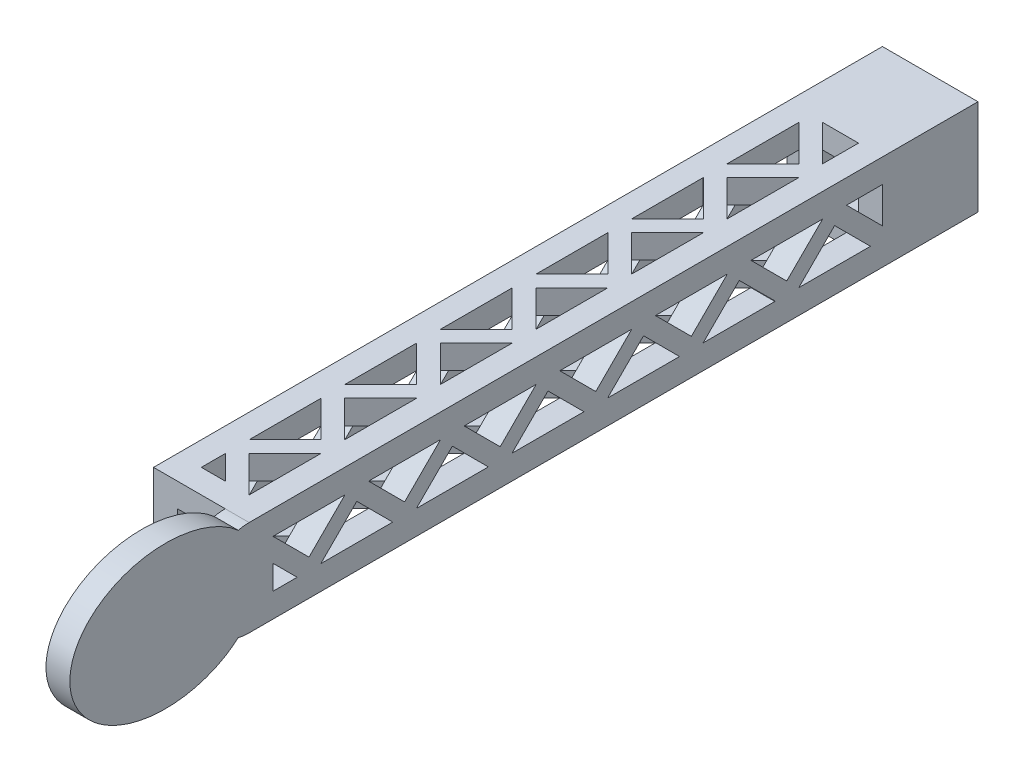
SolidWorks part; units mm, degrees
ref_plane "Front Plane" through (0, 0, 0) normal (0, 0, 1) x (1, 0, 0)
ref_plane "Top Plane" through (0, 0, 0) normal (0, 1, 0) x (1, 0, 0)
ref_plane "Right Plane" through (0, 0, 0) normal (1, 0, 0) x (0, 0, -1)
sketch "Sketch1" plane through (0, 0, 0) normal (0, 0, 1) x (1, 0, 0)
  line L1 (0, 0) -> (20.32, 0)
  line L2 (0, 0) -> (0, 20.32)
  line L3 (0, 20.32) -> (20.32, 20.32)
  line L4 (20.32, 0) -> (20.32, 20.32)
  line L5 (5.08, 15.24) -> (15.24, 15.24)
  line L6 (5.08, 15.24) -> (5.08, 5.08)
  line L7 (5.08, 5.08) -> (15.24, 5.08)
  line L8 (15.24, 15.24) -> (15.24, 5.08)
  dimension "D1" = 20.32
  dimension "D2" = 20.32
  dimension "D3" = 10.16
  dimension "D4" = 10.16
  dimension "D5" = 5.08
  dimension "D6" = 5.08
extrude "Boss-Extrude1" add sketch "Sketch1" along normal blind 154.94
sketch "Sketch6" plane through (0, 20.32, 0) normal (0, 1, 0) x (1, 0, 0)
  line L0 (20.32, 0) -> (20.32, -20.32) construction
  line L1 (20.32, -154.94) -> (20.32, 0) construction
  line L2 (20.32, -20.32) -> (15.24, -20.32) construction
  line L3 (0, 0) -> (0, -20.32) construction
  line L4 (0, -154.94) -> (0, 0) construction
  line L5 (0, -20.32) -> (5.08, -20.32) construction
  line L6 (7.62, -20.32) -> (15.24, -27.94)
  line L7 (7.62, -20.32) -> (15.24, -20.32)
  line L8 (5.08, -22.86) -> (5.08, -38.1)
  line L9 (5.08, -149.86) -> (10.2137, -149.86)
  line L10 (15.24, -20.32) -> (15.24, -27.94)
  line L11 (5.08, -22.86) -> (12.7, -30.48)
  line L12 (15.24, -33.02) -> (15.24, -48.26)
  line L13 (12.7, -30.48) -> (5.08, -38.1)
  line L14 (15.24, -33.02) -> (7.62, -40.64)
  line L15 (7.62, -40.64) -> (15.24, -48.26)
  line L16 (5.1337, -43.1263) -> (12.7335, -50.7665)
  line L17 (5.08, -43.18) -> (5.08, -58.42)
  line L18 (5.1337, -43.1263) -> (5.08, -43.18)
  line L19 (15.24, -53.2863) -> (7.5931, -60.9331)
  line L20 (12.7335, -50.7665) -> (5.08, -58.42)
  line L21 (7.5931, -60.9331) -> (15.24, -68.58)
  line L22 (5.08, -63.4463) -> (12.7269, -71.0931)
  line L23 (12.7269, -71.0931) -> (5.08, -78.74)
  line L24 (15.24, -73.6063) -> (7.5931, -81.2531)
  line L25 (5.08, -83.7663) -> (12.7269, -91.4131)
  line L26 (7.5931, -81.2531) -> (15.24, -88.9)
  line L27 (15.24, -53.2863) -> (15.24, -68.58)
  line L28 (5.08, -63.4463) -> (5.08, -78.74)
  line L29 (15.24, -73.6063) -> (15.24, -88.9)
  line L30 (5.08, -83.7663) -> (5.08, -99.06)
  line L31 (15.24, -93.9263) -> (15.24, -109.22)
  line L32 (15.24, -93.9263) -> (7.5931, -101.5731)
  line L33 (12.7269, -91.4131) -> (5.08, -99.06)
  line L34 (7.5931, -101.5731) -> (15.24, -109.22)
  line L35 (5.08, -104.0863) -> (12.7269, -111.7331)
  line L36 (12.7269, -111.7331) -> (5.08, -119.38)
  line L37 (15.24, -114.2463) -> (7.5931, -121.8931)
  line L38 (7.5931, -121.8931) -> (15.24, -129.54)
  line L39 (5.08, -124.4063) -> (12.7269, -132.0531)
  line L40 (12.7269, -132.0531) -> (5.08, -139.7)
  line L41 (15.24, -134.5663) -> (7.5931, -142.2131)
  line L42 (5.08, -144.7263) -> (10.2137, -149.86)
  line L43 (7.5931, -142.2131) -> (15.24, -149.86)
  line L44 (5.08, -144.7263) -> (5.08, -149.86)
  line L45 (15.24, -134.5663) -> (15.24, -149.86)
  line L46 (5.08, -124.4063) -> (5.08, -139.7)
  line L47 (15.24, -114.2463) -> (15.24, -129.54)
  line L48 (5.08, -104.0863) -> (5.08, -119.38)
  line M9 (20.32, 0) -> (0, 0)
  line M10 (0, 0) -> (0, -154.94)
  line M11 (0, -154.94) -> (20.32, -154.94)
  line M12 (20.32, -154.94) -> (20.32, 0)
  dimension "D1" = 20.32
  dimension "D2" = 5.08
  dimension "D3" = 5.08
  dimension "D4" = 20.32
  dimension "D5" = 129.54
  dimension "D7" = 10.16
  dimension "D8" = 7.62
  dimension "D10" = 5.08
  dimension "D9" = 2.54
  dimension "D6" = 2.54
  dimension "D11" = 10.16
  dimension "D12" = 10.16
  dimension "D13" = 10.16
  dimension "D14" = 10.16
  dimension "D15" = 10.16
  dimension "D16" = 10.16
  dimension "D17" = 10.16
  dimension "D18" = 10.16
  dimension "D19" = 10.16
  dimension "D20" = 10.16
  dimension "D21" = 10.16
  dimension "D22" = 10.16
  dimension "D23" = 10.16
  dimension "D24" = 10.16
  dimension "D25" = 10.16
  dimension "D26" = 10.16
  dimension "D27" = 10.16
  dimension "D28" = 10.16
  dimension "D29" = 10.16
  dimension "D30" = 10.16
  dimension "D31" = 10.16
  dimension "D32" = 10.16
  dimension "D33" = 10.16
extrude "Cut-Extrude1" cut sketch "Sketch6" against normal through all flip side to cut contours L48 L35 L36 L46 L39 L40 L44 L42 L9 L34 L32 L31 L28 L22 L23 L15 L14 L12 L7 L10 L6 L11 L13 L8 L16 L20 L17 L18 L19 L27 L21 L24 L29 L26 L25 M12 M9 M10 M11 region at (10.148, 20.32, 75.1438)
sketch "Sketch8" plane through (0, -104.6928, 116.6569) normal (-1, 0, 0) x (0, 1, 0)
  line L0 (104.6928, -38.2831) -> (104.6928, 116.6569) construction
  line L2 (104.6928, 116.6569) -> (104.6928, 96.3369) construction
  line L3 (104.6928, 96.3369) -> (109.7728, 96.3369) construction
  line L4 (112.3128, 96.3369) -> (119.9328, 88.7169)
  line L5 (112.3128, 96.3369) -> (119.9328, 96.3369)
  line L6 (109.8286, 93.7969) -> (109.8286, 78.5569)
  line L7 (109.8286, -33.2031) -> (114.9623, -33.2031)
  line L8 (119.9328, 96.3369) -> (119.9328, 88.7169)
  line L9 (109.8286, 93.7969) -> (117.4486, 86.1769)
  line L10 (119.9328, 83.6369) -> (119.9328, 68.3969)
  line L11 (117.4486, 86.1769) -> (109.8286, 78.5569)
  line L12 (119.9328, 83.6369) -> (112.3338, 75.996)
  line L13 (112.3338, 75.996) -> (119.9328, 68.3969)
  line L14 (109.882, 73.5306) -> (117.4923, 65.9009)
  line L15 (109.8286, 73.4769) -> (109.8286, 58.2369)
  line L16 (109.882, 73.5306) -> (109.8286, 73.4769)
  line L17 (119.9328, 63.3706) -> (112.286, 55.7238)
  line L18 (117.4923, 65.9009) -> (109.8286, 58.2369)
  line L19 (112.286, 55.7238) -> (119.9328, 48.0769)
  line L20 (109.8286, 53.2106) -> (117.4754, 45.5638)
  line L21 (117.4754, 45.5638) -> (109.8286, 37.9169)
  line L22 (119.9328, 43.0506) -> (112.286, 35.4038)
  line L23 (109.8286, 32.8906) -> (117.4754, 25.2438)
  line L24 (112.286, 35.4038) -> (119.9328, 27.7569)
  line L25 (119.9328, 63.3706) -> (119.9328, 48.0769)
  line L26 (109.8286, 53.2106) -> (109.8286, 37.9169)
  line L27 (119.9328, 43.0506) -> (119.9328, 27.7569)
  line L28 (109.8286, 32.8906) -> (109.8286, 17.5969)
  line L29 (119.9328, 22.7306) -> (119.9328, 7.4369)
  line L30 (119.9328, 22.7306) -> (112.286, 15.0838)
  line L31 (117.4754, 25.2438) -> (109.8286, 17.5969)
  line L32 (112.286, 15.0838) -> (119.9328, 7.4369)
  line L33 (109.8286, 12.5706) -> (117.4754, 4.9238)
  line L34 (117.4754, 4.9238) -> (109.8286, -2.7231)
  line L35 (119.9328, 2.4106) -> (112.286, -5.2362)
  line L36 (112.286, -5.2362) -> (119.9328, -12.8831)
  line L37 (109.8286, -7.7494) -> (117.4754, -15.3962)
  line L38 (117.4754, -15.3962) -> (109.8286, -23.0431)
  line L39 (119.9328, -17.9094) -> (112.286, -25.5562)
  line L40 (109.8286, -28.0694) -> (114.9623, -33.2031)
  line L41 (112.286, -25.5562) -> (119.9328, -33.2031)
  line L42 (109.8286, -28.0694) -> (109.8286, -33.2031)
  line L43 (119.9328, -17.9094) -> (119.9328, -33.2031)
  line L44 (109.8286, -7.7494) -> (109.8286, -23.0431)
  line L45 (119.9328, 2.4106) -> (119.9328, -12.8831)
  line L46 (109.8286, 12.5706) -> (109.8286, -2.7231)
  line L49 (125.0128, 116.6569) -> (104.6928, 116.6569) construction
  point P3 (96.7014, -49.2233)
  point P51 (172.1584, -100.6537)
  dimension "D3" = 5.08
  dimension "D4" = 20.32
  dimension "D5" = 129.54
  dimension "D6" = 10.16
  dimension "D7" = 7.62
  dimension "D8" = 5.08
  dimension "D9" = 2.54
  dimension "D10" = 2.54
  dimension "D11" = 10.16
  dimension "D12" = 10.16
  dimension "D13" = 10.16
  dimension "D14" = 10.16
  dimension "D15" = 10.16
  dimension "D16" = 10.16
  dimension "D17" = 10.16
  dimension "D18" = 10.16
  dimension "D19" = 10.16
  dimension "D20" = 10.16
  dimension "D21" = 10.16
  dimension "D22" = 10.16
  dimension "D23" = 10.16
  dimension "D24" = 10.16
  dimension "D25" = 10.16
  dimension "D26" = 10.16
  dimension "D27" = 10.16
  dimension "D28" = 10.16
  dimension "D29" = 10.16
  dimension "D30" = 10.16
  dimension "D31" = 10.16
  dimension "D32" = 10.16
  dimension "D33" = 10.16
  dimension "D34" = 20.32
  dimension "D35" = 5.1337
  dimension "D36" = 15.2937
  dimension "D38" = 15.2937
extrude "Cut-Extrude6" cut sketch "Sketch8" against normal through all contours L11 L9 L6 | L12 L13 L10 | L25 L17 L19 | L20 L26 L21 | L27 L22 L24 | L31 L23 L28 | L30 L32 L29 | L33 L46 L34 | L45 L35 L36 | L43 L39 L41 | L40 L42 L7 | L14 L18 L15 L16 | L5 L8 L4 | L37 L38 L44 region at (0, 7.6757, 30.48) region at (0, 6.847, 148.1488) region at (0, 12.707, 40.647) region at (0, 12.691, 60.9331) region at (0, 7.6847, 71.0931) region at (0, 12.691, 81.2531) region at (0, 7.6847, 91.4131) region at (0, 12.691, 101.5731) region at (0, 7.6847, 111.7331) region at (0, 12.691, 121.8931) region at (0, 12.691, 142.2131)
sketch "Sketch10" plane through (20.32, 0, 0) normal (1, 0, 0) x (0, 0, -1)
  line L0 (-154.94, 0) -> (-154.94, 20.32) construction
  line L1 (-172.72, 25.4) -> (-172.72, -5.08) construction
  line L2 (-154.94, 20.32) -> (-154.94, 0)
  arc A2 (-157.2613, 0.2687) -> (-154.94, 0) centre (-154.94, 10.16) ccw
  arc A3 (-154.94, 20.32) -> (-157.2613, 20.0513) centre (-154.94, 10.16) ccw
  ellipse E0 centre (-172.72, 10.16) end of major axis (-193.04, 10.16) minor radius 15.24 (-157.2613, 20.0513) -> (-157.2613, 0.2687) ccw
  point P4 (-154.94, 10.16)
  dimension "D1" = 17.78
extrude "Boss-Extrude2" add sketch "Sketch10" against normal blind 5.08
equation "\"D2@Sketch1\"=\"D1@Sketch1\""
equation "\"D3@Sketch1\"=\"D1@Sketch1\"-0.4"
equation "\"D4@Sketch1\"=\"D3@Sketch1\""
equation "\"D3@Sketch6\"=\"D2@Sketch6\""
equation "\"D4@Sketch6\"=\"D1@Sketch6\""
